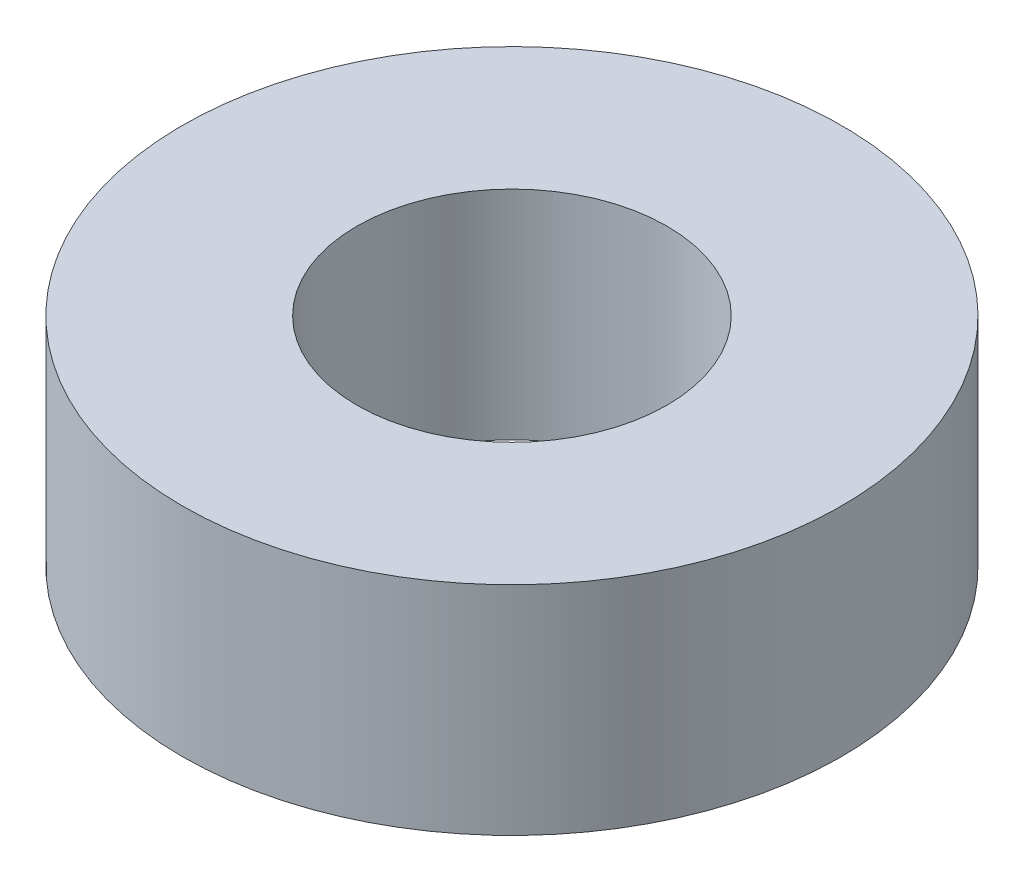
SolidWorks part; units mm, degrees
ref_plane "Front Plane" through (0, 0, 0) normal (0, 0, 1) x (1, 0, 0)
ref_plane "Top Plane" through (0, 0, 0) normal (0, 1, 0) x (1, 0, 0)
ref_plane "Right Plane" through (0, 0, 0) normal (1, 0, 0) x (0, 0, -1)
sketch "Sketch1" plane through (0, 0, 0) normal (0, 1, 0) x (1, 0, 0)
  circle A0 centre (0, 0) radius 42.5
  dimension "FLANGE_OD" = 85
extrude "Boss-Extrude1" add sketch "Sketch1" along normal blind 28
sketch "Sketch2" plane through (0, 0, 0) normal (0, 1, 0) x (1, 0, 0)
  circle A0 centre (0, 0) radius 20
  dimension "BORE_D" = 40
extrude "Cut-Extrude1" cut sketch "Sketch2" along normal through all
sketch "Sketch3" plane through (0, 28, 0) normal (0, 1, 0) x (1, 0, 0)
  circle A0 centre (0, 0) radius 15.139 construction
  circle A1 centre (-15.139, 0) radius 2.5783
  dimension "BOLT_D" = 5.1566
  dimension "BOLT_PCD" = 30.278
extrude "Cut-Extrude2" cut sketch "Sketch3" against normal blind 23.2541 rebuild error yes
pattern_circular "CirPattern1" count 4 over 360 rebuild error yes
